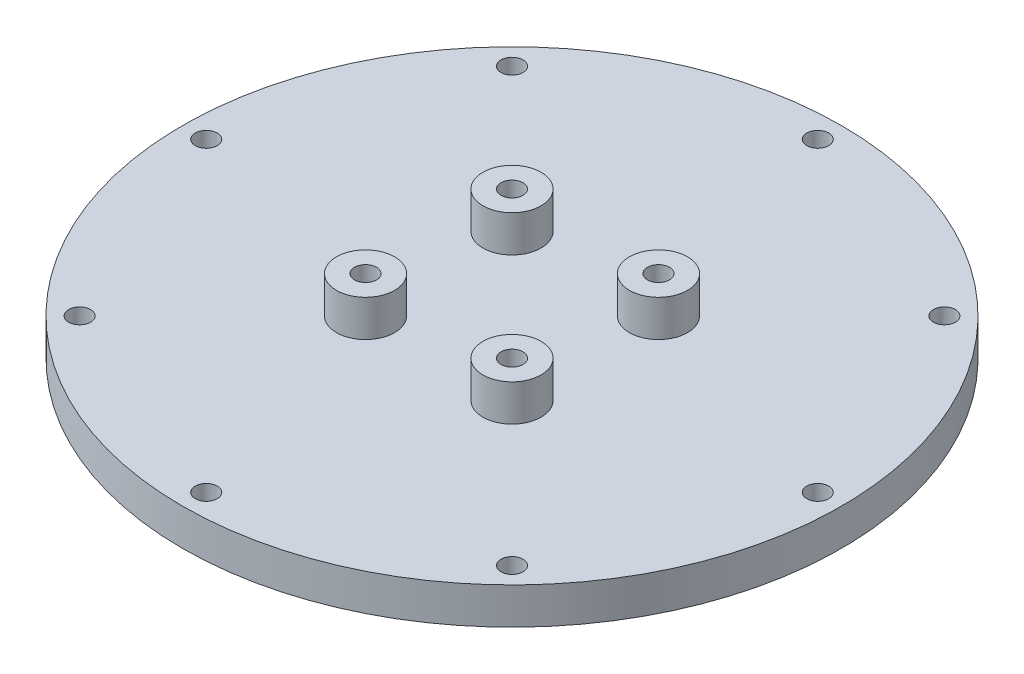
SolidWorks part; units mm, degrees
ref_plane "Front Plane" through (0, 0, 0) normal (0, 0, 1) x (1, 0, 0)
ref_plane "Top Plane" through (0, 0, 0) normal (0, 1, 0) x (1, 0, 0)
ref_plane "Right Plane" through (0, 0, 0) normal (1, 0, 0) x (0, 0, -1)
sketch "Sketch1" plane through (0, 0, 0) normal (0, 1, 0) x (1, 0, 0)
  circle A0 centre (0, 0) radius 45
  circle A1 centre (0, 41.75) radius 1.5
  circle A2 centre (29.5217, 29.5217) radius 1.5
  circle A3 centre (41.75, 0) radius 1.5
  circle A4 centre (29.5217, -29.5217) radius 1.5
  circle A5 centre (0, -41.75) radius 1.5
  circle A6 centre (-29.5217, -29.5217) radius 1.5
  circle A7 centre (-41.75, 0) radius 1.5
  circle A8 centre (-29.5217, 29.5217) radius 1.5
  point P22 (0, 0)
  dimension "D1" = 8
extrude "Boss-Extrude2" add sketch "Sketch1" along normal blind 5
sketch "Sketch2" plane through (0, 5, 0) normal (0, 1, 0) x (1, 0, 0)
  line L5 (-20, -20) -> (20, 20) construction
  line L6 (-20, 20) -> (20, -20) construction
  circle A0 centre (-10, 10) radius 3.9688
  circle A1 centre (10, 10) radius 3.9687
  circle A2 centre (10, -10) radius 3.9687
  circle A3 centre (-10, -10) radius 3.9688
  point P0 (0, 0)
  dimension "D4" = 2
  dimension "D1" = 40
  dimension "D2" = 40
  dimension "D3" = 2
extrude "Boss-Extrude3" add sketch "Sketch2" along normal blind 5
sketch "Sketch3" plane through (0, 10, 0) normal (0, 1, 0) x (1, 0, 0)
  circle A0 centre (-10, 10) radius 1.5
  circle A1 centre (10, 10) radius 1.5
  circle A2 centre (-10, -10) radius 1.5
  circle A3 centre (10, -10) radius 1.5
extrude "Cut-Extrude1" cut sketch "Sketch3" against normal blind 7
